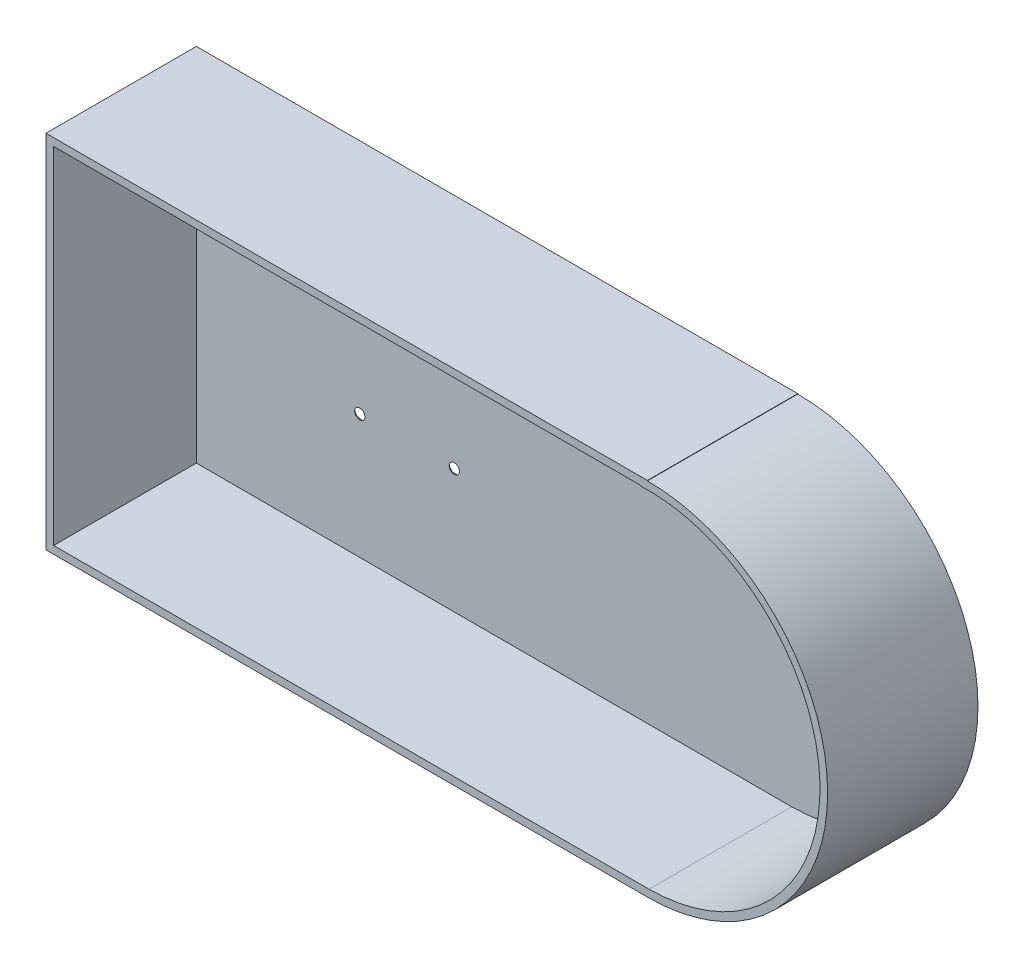
SolidWorks part; units mm, degrees
ref_plane "Front Plane" through (0, 0, 0) normal (0, 0, 1) x (1, 0, 0)
ref_plane "Top Plane" through (0, 0, 0) normal (0, 1, 0) x (1, 0, 0)
ref_plane "Right Plane" through (0, 0, 0) normal (1, 0, 0) x (0, 0, -1)
sketch "Sketch2" plane through (0, 0, 0) normal (0, 0, 1) x (1, 0, 0)
  line L0 (-59.8621, 43.4458) -> (-59.8621, 43.4483)
  line L1 (-259.8621, 163.4483) -> (-59.8621, 163.4483)
  line L2 (-259.8621, 163.4483) -> (-259.8621, 43.4483)
  line L3 (-259.8621, 43.4483) -> (-59.8621, 43.4483)
  line L4 (-59.8621, 163.4483) -> (-59.8621, 163.3289)
  line L5 (-59.8621, 43.4458) -> (-59.8621, 43.4483) construction
  line L6 (-59.8621, 163.3289) -> (-59.8621, 163.4483) construction
  arc A0 (-59.8621, 43.4458) -> (-59.8621, 163.3289) centre (-59.8622, 103.3873) ccw
  point P0 (-59.8621, 43.4483)
  point P7 (-59.9434, 43.527)
  point P10 (0, 0)
  point P11 (0, 0)
  point P12 (0, 0)
  point P13 (0, 0)
  point P14 (0, 0)
  point P15 (0, 0)
  point P16 (0, 0)
  point P17 (0, 0)
  point P18 (0, 0)
  point P19 (-59.8675, 163.4412)
  point P21 (-59.8301, 43.4232)
  dimension "D3" = 119.883
  dimension "D1" = 120
  dimension "D2" = 200
extrude "Boss-Extrude1" add sketch "Sketch2" along normal blind 50 contours L1 L4 A0 L0 L3 L2
shell "Shell1" thickness 2.54 removed face at (-116.5385, 103.428, 50)
sketch "Sketch3" plane through (0, 0, 0) normal (0, 0, -1) x (-1, 0, 0)
  circle A1 centre (75.4989, 103.7303) radius 45
extrude "Cut-Extrude1" cut sketch "Sketch3" against normal blind 1.74
sketch "Sketch4" plane through (0, 0, 0) normal (0, 0, -1) x (-1, 0, 0)
  line L0 (259.8621, 163.4483) -> (59.8621, 163.4483) construction
  line L13 (167.2862, 123.4483) -> (207.2862, 123.4483)
  line L14 (167.2862, 123.4483) -> (167.2862, 83.4483)
  line L15 (167.2862, 83.4483) -> (207.2862, 83.4483)
  line L16 (207.2862, 123.4483) -> (207.2862, 83.4483)
  dimension "D1" = 40
  dimension "D2" = 40
  dimension "D3" = 40
extrude "Cut-Extrude2" cut sketch "Sketch4" against normal blind 1.74
hole_wizard "Ø1.0mm Dowel Hole1" positions "Sketch6" profile "Sketch8" hole size "Ø1.0" standard "DIN"
sketch "Sketch6" plane through (0, 0, 1.74) normal (0, 0, -1) x (-1, 0, 0)
  point P0 (72.666, 104.2969)
  point P3 (171.5356, 118.4616)
  point P5 (202.9812, 118.4616)
  point P7 (202.9812, 87.2993)
  point P9 (171.5356, 87.2993)
  point P12 (0, 0)
sketch "Sketch8" plane through (-72.666, 104.2969, 1.74) normal (1, 0, 0) x (0, 1, 0)
  line L0 (0, 0) -> (0, 1.5704)
  line L1 (0, 1.5704) -> (0.5, 1.27)
  line L2 (0.5, 1.27) -> (0.5, 2)
  line L3 (0.5, 2) -> (2.5, 0)
  line L5 (2.5, 0) -> (0, 0)
  line L6 (-0.5, 2) -> (-2.5, 0) construction
  line L10 (0, 1.5704) -> (-0.5, 1.27) construction
  line L11 (0, -6.35) -> (0, 107.95) construction
  dimension "Hole Dia." = 1
  dimension "Hole Depth" = 1.27
  dimension "Near C'Sink Dia." = 5
  dimension "Near C'Sink Angle" = 90
  dimension "Drill Angle" = 118
